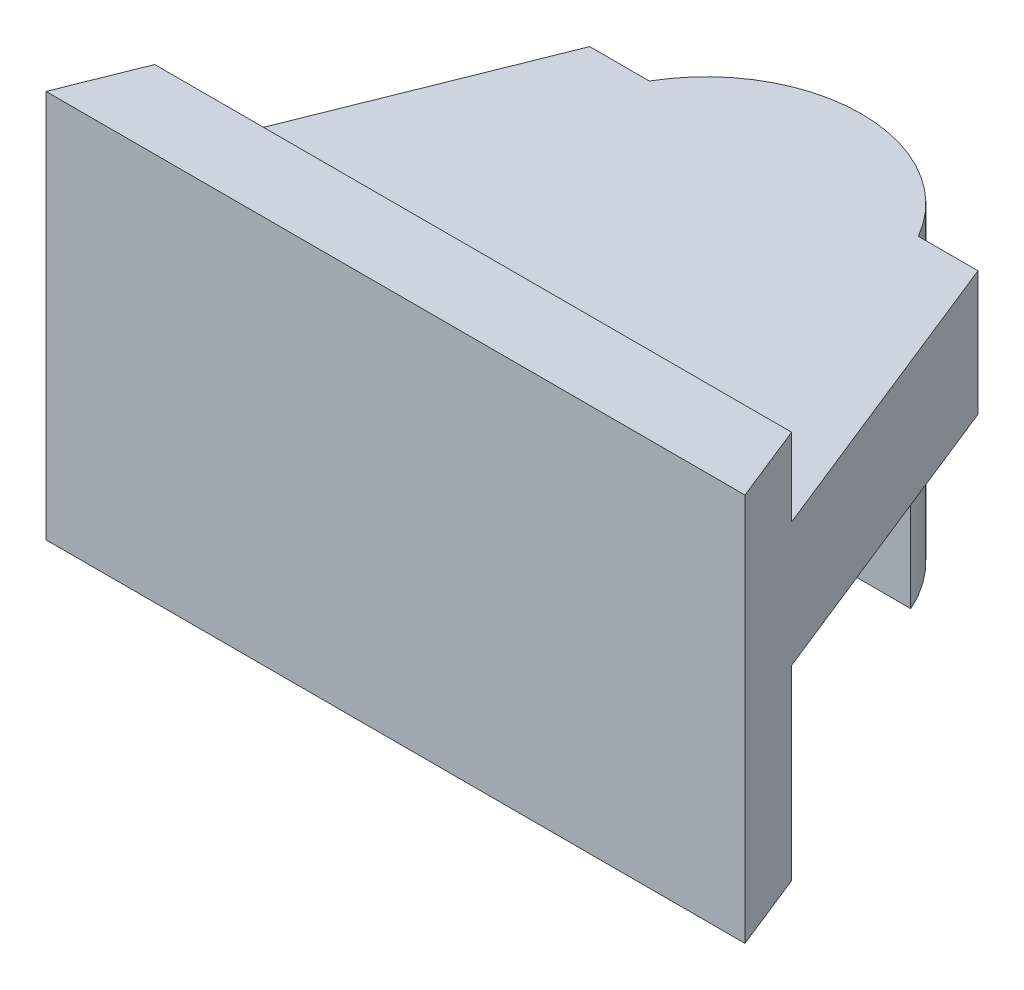
SolidWorks part; units mm, degrees
ref_plane "Front Plane" through (0, 0, 0) normal (0, 0, 1) x (1, 0, 0)
ref_plane "Top Plane" through (0, 0, 0) normal (0, 1, 0) x (1, 0, 0)
ref_plane "Right Plane" through (0, 0, 0) normal (1, 0, 0) x (0, 0, -1)
sketch "Sketch3" plane through (0, 0, 0) normal (0, 1, 0) x (1, 0, 0)
  circle A0 centre (0, 0) radius 20
  dimension "D1" = 40
extrude "Boss-Extrude1" add sketch "Sketch3" along normal blind 40
sketch "Sketch4" plane through (0, 40, 0) normal (0, 1, 0) x (1, 0, 0)
  line L1 (25, 10) -> (45, -40)
  line L2 (45, -40) -> (-45, -40)
  line L3 (-45, -40) -> (-25, 10)
  line L4 (0, 39.936) -> (0, -42.7504) construction
  line L5 (-25, 10) -> (-17.3205, 10)
  line L6 (-17.3205, 10) -> (17.3205, 10)
  line L7 (17.3205, 10) -> (25, 10)
  circle A0 centre (0, 0) radius 20 construction
  dimension "D1" = 50
  dimension "D2" = 90
  dimension "D4" = 40
extrude "Boss-Extrude2" add sketch "Sketch4" along normal blind 16 from offset 16 offset against normal yes
sketch "Sketch6" plane through (0, 24, 0) normal (0, -1, 0) x (-1, 0, 0)
  line L0 (-41, -30) -> (41, -30)
  line L1 (-45, -40) -> (-25, 10) construction
  line L2 (25, 10) -> (45, -40) construction
  line L3 (41, -30) -> (45, -40)
  line L4 (45, -40) -> (-45, -40)
  line L5 (-45, -40) -> (-41, -30)
  dimension "D1" = 10
extrude "Boss-Extrude3" add sketch "Sketch6" along normal blind 50 from offset 26 offset against normal yes
sketch "Sketch7" plane through (0, 24, 0) normal (0, -1, 0) x (-1, 0, 0)
  line L0 (-6, -30) -> (-6, -19.0788)
  line L1 (-41, -30) -> (41, -30) construction
  line L3 (6, -19.0788) -> (6, -30)
  line L4 (41, -30) -> (-41, -30) construction
  line L5 (6, -30) -> (-6, -30)
  line L6 (6, -30) -> (-6, -30)
  line L7 (-24.0049, 8) -> (23.6794, 8)
  line L8 (23.6794, 8) -> (23.6794, -8)
  line L9 (23.6794, -8) -> (-24.0049, -8)
  line L10 (-24.0049, -8) -> (-24.0049, 8)
  arc A0 (-17.3205, 10) -> (17.3205, 10) centre (0, 0) ccw construction
  circle A1 centre (0, 0) radius 20 construction
  point P7 (0, -30)
  point P21 (-24.0049, 0)
  line M2 (-41, -30) -> (41, -30)
  arc M5 (17.3205, 10) -> (-17.3205, 10) centre (0, 0) cw
  dimension "D1" = 12
  dimension "D2" = 16
extrude "Boss-Extrude4" add sketch "Sketch7" along normal blind 20 contours L3 L0 M5 M2 region at (0, 24, 24.8443)
extrude "Cut-Extrude1" cut sketch "Sketch7<3>" along normal blind 12 from offset 12 contours L9 L7 M5 region at (0, 24, 0)
sketch "Sketch7<3>" plane through (0, 24, 0) normal (0, -1, 0) x (-1, 0, 0) same geometry as "Sketch7"
